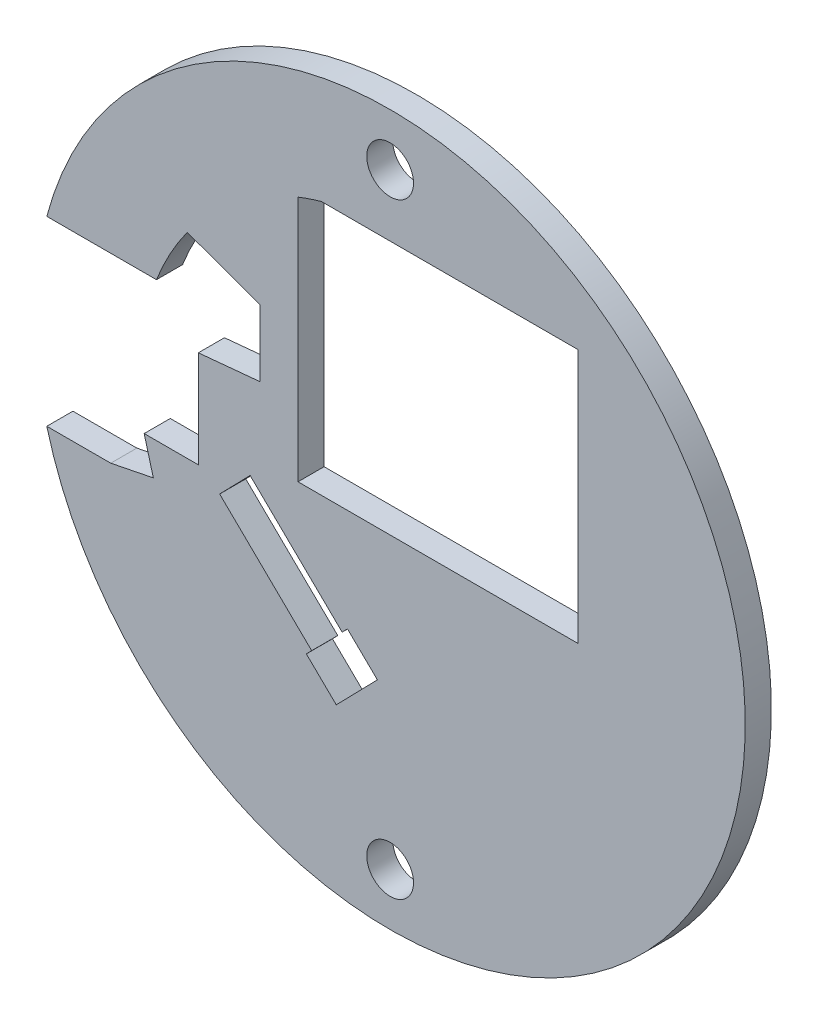
SolidWorks part; units mm, degrees
ref_plane "Front Plane" through (0, 0, 0) normal (0, 0, 1) x (1, 0, 0)
ref_plane "Top Plane" through (0, 0, 0) normal (0, 1, 0) x (1, 0, 0)
ref_plane "Right Plane" through (0, 0, 0) normal (1, 0, 0) x (0, 0, -1)
sketch "Sketch1" plane through (0, 0, 0) normal (0, 0, 1) x (1, 0, 0)
  line L0 (-11.6599, 2.9485) -> (-11.6599, -2.9485)
  line L1 (-15.24, 0) -> (-11.6599, 0) construction
  line L2 (-11.6599, 2.9485) -> (-14.9521, 2.9485)
  line L3 (-11.6599, -2.9485) -> (-14.9521, -2.9485)
  line L4 (-11.6599, 2.9485) -> (-7.9248, 3.302)
  line L5 (-20.8712, -5.5245) -> (-16.9841, -5.5245)
  line L6 (-16.9841, -5.5245) -> (-14.3951, -5.0038)
  line L7 (-14.2034, 5.5245) -> (-20.8712, 5.5245)
  line L8 (-14.3951, -5.0038) -> (-14.9521, -2.9485)
  line L9 (-14.9521, 2.9485) -> (-14.2034, 5.5245)
  line B0 (-15.24, 18.2372) -> (15.24, 18.2372)
  line B1 (11.43, 14.6558) -> (11.43, -0.8128)
  line B2 (0, 18.2372) -> (0, 0) construction
  line B3 (-5.6007, 14.1736) -> (-5.6007, -0.8128)
  line B4 (11.43, 14.6558) -> (-4.1791, 14.6558)
  line B5 (-5.6007, -0.8128) -> (11.43, -0.8128)
  line B6 (7.8232, -4.064) -> (12.3063, -4.064)
  line B7 (11.43, -0.8128) -> (12.3063, -0.8128)
  line B8 (12.3063, -0.8128) -> (12.3063, -4.064)
  line B9 (7.8232, -7.3406) -> (1.2573, -7.3406)
  line B10 (7.8232, -4.064) -> (7.8232, -7.3406)
  line B11 (-4.3942, -0.8128) -> (-4.3942, -4.064)
  line B12 (-4.3942, -4.064) -> (1.2573, -4.064)
  line B13 (1.2573, -4.064) -> (1.2573, -7.3406)
  line B14 (-0.7747, -8.8265) -> (-3.2737, -11.3919)
  line B15 (-0.7747, -8.8265) -> (-2.5941, -7.0541)
  line B16 (-2.5941, -7.0541) -> (-2.9176, -7.3862)
  line B17 (-2.9176, -7.3862) -> (-8.5123, -1.9362)
  line B18 (-8.5123, -1.9362) -> (-10.3645, -3.8375)
  line B19 (-10.3645, -3.8375) -> (-4.7697, -9.2875)
  line B20 (-4.7697, -9.2875) -> (-5.0932, -9.6195)
  line B21 (-5.0932, -9.6195) -> (-3.2737, -11.3919)
  line B22 (-12.3326, 18.2372) -> (-12.3326, 8.9535)
  line B23 (-7.9248, 18.2372) -> (-7.9248, 7.366) construction
  line B24 (-12.3326, 8.9535) -> (-7.9248, 7.366)
  line B25 (-5.6007, 3.302) -> (-7.9248, 3.302)
  line B26 (-7.9248, 3.302) -> (-7.9248, 7.366)
  line B27 (-14.3951, -5.0038) -> (-9.1672, -5.0038)
  line B28 (-0.7747, -8.8265) -> (1.2573, -7.3406)
  arc B29 (-3.302, 14.878) -> (3.302, 14.878) centre (0, 0) ccw
  circle B30 centre (0, -18.415) radius 1.4224
  circle B31 centre (0, 18.415) radius 1.4224
  circle B32 centre (0, 0) radius 21.59
  dimension "D1" = 1.2954
  dimension "D2" = 3.2922
sketch_block_instance "Puslar Top Layout-1"
sketch_block "Puslar Top Layout" parameters "D1"=3.81, "D2"=30.48, "D3"=3.5814, "D4"=9.6393, "D5"=19.05, "D6"=22.3012, "D7"=0.8763, "D8"=4.4831, "D9"=6.5278, "D10"=6.5659, "D11"=5.6515, "D12"=27.0637, "D13"=29.6291, "D14"=3.5814, "D15"=14.4653, "D16"=2.54, "D17"=2.6543, "D18"=10.3505, "D19"=9.2837, "D20"=10.8712, "D21"=7.3152, "D22"=14.9352, "D23"=23.241
extrude "Boss-Extrude2" add sketch "Sketch1" along normal blind 1.5875 contours B22 B32 B29 | L3 B29 B27 B19 B18 B17 B16 B15 B28 B13 B12 B11 B5 B3 B25 L4 L0 | B0 B32 B22 B29 B4 B1 B31 B30 | B27 B29 B1 B7 B8 B6 B10 B9 B28 B14 B21 B20 B19 | B12 B13 B9 B10 B6 B8 B7 B5 B11 | B0 B32 B31 | B3 B29 B24 B26 B25 region at (-6.7767, -2.3728, 0) region at (-7.7282, 8.9883, 0) region at (-15.702, 10.2546, 0) region at (7.98, -13.6624, 0) region at (3.0061, -7.6086, 0) region at (4.1218, -3.3646, 0) region at (0, 21.3565, 0)
